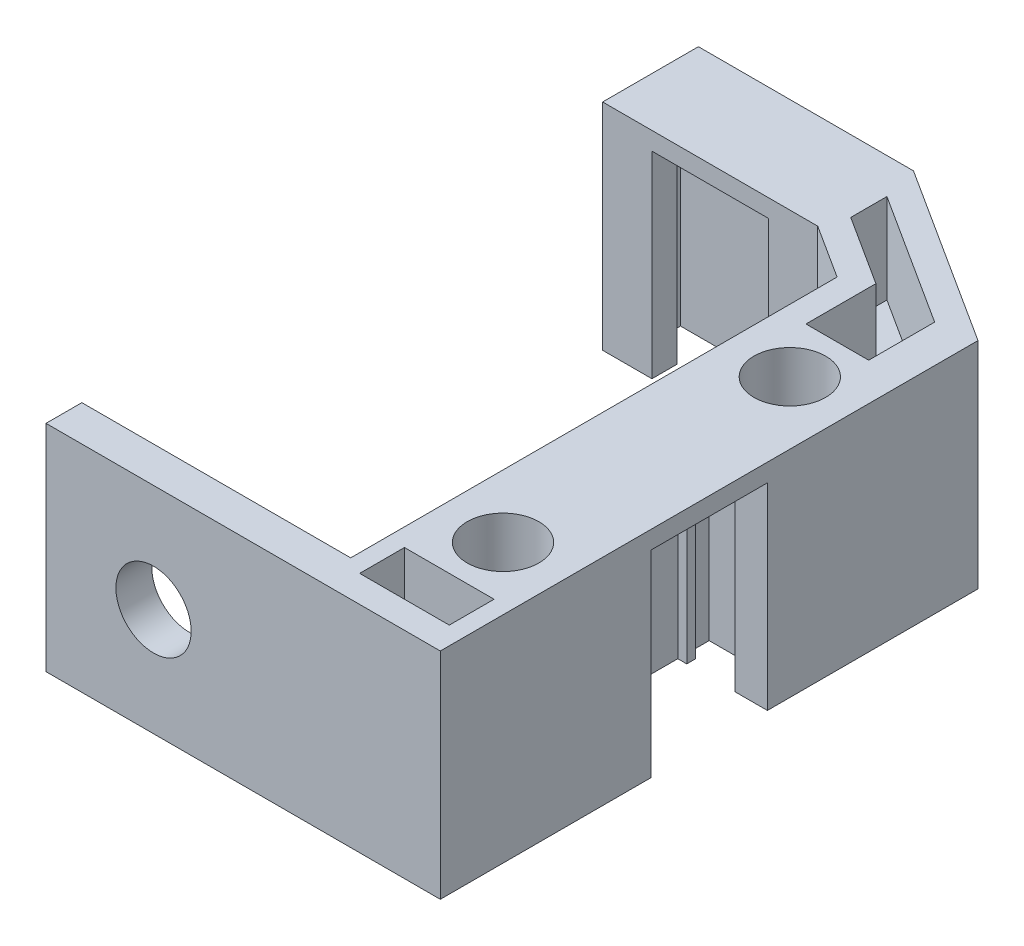
SolidWorks part; units mm, degrees
ref_plane "前视基准面" through (0, 0, 0) normal (0, 0, 1) x (1, 0, 0)
ref_plane "上视基准面" through (0, 0, 0) normal (0, 1, 0) x (1, 0, 0)
ref_plane "右视基准面" through (0, 0, 0) normal (1, 0, 0) x (0, 0, -1)
other "Configuration Table"
sketch "草图1" plane through (0, 0, 0) normal (0, 1, 0) x (1, 0, 0)
  line L0 (0, 0) -> (0, 2)
  line L1 (0, 36.4) -> (12, 36.4)
  line L2 (12, 36.4) -> (22, 30)
  line L3 (22, 30) -> (22, 0)
  line L4 (22, 0) -> (0, 0)
  line L5 (0, 31.0573) -> (12, 31.0573)
  line L6 (12, 31.0573) -> (15, 29.1373)
  line L7 (15, 29.1373) -> (15, 2)
  line L8 (15, 2) -> (0, 2)
  line L9 (0, 31.0573) -> (0, 36.4)
  point P11 (17, 33.2)
  dimension "D1" = 22
  dimension "D2" = 36.4
  dimension "D3" = 30
  dimension "D4" = 12
  dimension "D5" = 2
  dimension "D6" = 7
  dimension "D7" = 4.5
extrude "凸台-拉伸1" add sketch "草图1" along normal blind 12
sketch "草图2" plane through (0, 0, 0) normal (0, -1, 0) x (1, 0, 0)
  line L0 (12, -36.4) -> (0, -36.4) construction
  line L1 (1, -34.4) -> (11, -34.4)
  line L2 (1, -34.4) -> (1, -32.4573)
  line L3 (1, -32.4573) -> (2.75, -32.4573)
  line L4 (11, -34.4) -> (11, -32.4573)
  line L5 (1, -34.4) -> (11, -32.4573) construction
  line L6 (1, -32.4573) -> (11, -34.4) construction
  line L7 (0, -31.0573) -> (12, -31.0573) construction
  line L8 (0, -36.4) -> (0, -31.0573) construction
  line L9 (12.5, -32.3995) -> (12.5, -34.4178)
  line L10 (12.5, -34.4178) -> (19.9, -29.6818)
  line L11 (19.9, -29.6818) -> (19.9, -26)
  line L12 (19.9, -26) -> (16.4, -26)
  line L13 (16.4, -26) -> (16.4, -29.9035)
  line L14 (16.4, -29.9035) -> (12.5, -32.3995)
  line L15 (22, -30) -> (12, -36.4) construction
  line L16 (22, 0) -> (22, -30) construction
  line L17 (12, -31.0573) -> (15, -29.1373) construction
  line L18 (22, -30) -> (15, -30.369) construction
  line L19 (15, -29.1373) -> (15, -2) construction
  line L20 (17, -20) -> (17, -18.75)
  line L21 (17, -18.75) -> (17.5, -18.75)
  line L22 (17.5, -18.75) -> (17.5, -18.25)
  line L23 (17.5, -18.25) -> (17, -18.25)
  line L24 (17, -18.25) -> (17, -11.75)
  line L25 (17, -11.75) -> (17.5, -11.75)
  line L26 (17.5, -11.75) -> (17.5, -11.25)
  line L27 (17.5, -11.25) -> (17, -11.25)
  line L28 (17, -11.25) -> (17, -10)
  line L29 (17, -10) -> (20.2, -10)
  line L30 (20.2, -10) -> (20.2, -11.75)
  line L31 (20.2, -11.75) -> (22, -11.75)
  line L32 (22, -11.75) -> (22, -18.25)
  line L33 (22, -18.25) -> (20.2, -18.25)
  line L34 (20.2, -18.25) -> (20.2, -20)
  line L35 (20.2, -20) -> (17, -20)
  line L36 (22, 0) -> (22, -30) construction
  line L37 (22, -15) -> (15, -15) construction
  line L38 (0, 0) -> (22, 0) construction
  line L39 (16, -4) -> (21, -4)
  line L40 (16, -4) -> (16, -1.5)
  line L41 (16, -1.5) -> (21, -1.5)
  line L42 (21, -4) -> (21, -1.5)
  line L43 (16, -4) -> (21, -1.5) construction
  line L44 (16, -1.5) -> (21, -4) construction
  line L45 (2.75, -32.4573) -> (2.75, -31.0573)
  line L46 (2.75, -31.0573) -> (9.25, -31.0573)
  line L47 (9.25, -31.0573) -> (9.25, -32.4573)
  line L48 (9.25, -32.4573) -> (11, -32.4573)
  circle A0 centre (18.5, -23) radius 2
  circle A1 centre (18.5, -7) radius 2
  point P4 (6, -33.4287)
  point P44 (15, -15.5687)
  point P53 (18.5, -15)
  point P62 (18.5, -2.75)
  line M46 (22, -30) -> (22, 0)
  dimension "D17" = 4
  dimension "D1" = 10
  dimension "D2" = 2
  dimension "D3" = 1.4
  dimension "D4" = 1
  dimension "D5" = 3.5
  dimension "D6" = 1.4
  dimension "D7" = 1.4
  dimension "D8" = 1.5
  dimension "D9" = 1.4
  dimension "D10" = 2
  dimension "D11" = 1.8
  dimension "D12" = 6.5
  dimension "D13" = 10
  dimension "D14" = 0.5
  dimension "D15" = 0.5
  dimension "D16" = 0.5
  dimension "D19" = 16
  dimension "D18" = 3
  dimension "D20" = 3
  dimension "D21" = 1.5
  dimension "D22" = 2
  dimension "D23" = 1
  dimension "D24" = 3
  dimension "D25" = 6.5
  dimension "D26" = 1.75
extrude "切除-拉伸1" cut sketch "草图2" against normal blind 5 contours L13 L14 L9 L10 L11 L12 | L39 L42 L41 L40 region at (16.8771, 0, -29.6298) region at (18.5, 0, -2.75)
extrude "切除-拉伸3" cut sketch "草图2<3>" along normal blind 5 from surface contours L13 L14 L9 L10 L11 L12 | L39 L42 L41 L40 region at (16.8771, 0, -29.6298) region at (18.5, 0, -2.75) starting at face at (9.8, 12, -19.8052)
sketch "草图2<3>" plane through (0, 0, 0) normal (0, -1, 0) x (1, 0, 0) same geometry as "草图2"
extrude "切除-拉伸4" cut sketch "草图2<4>" against normal through all contours A0 | A1 region at (18.5, 0, -23) region at (18.5, 0, -7)
sketch "草图2<4>" plane through (0, 0, 0) normal (0, -1, 0) x (1, 0, 0) same geometry as "草图2"
extrude "切除-拉伸5" cut sketch "草图2<5>" against normal blind 11 contours L35 L34 L33 L31 L30 L29 L28 L27 L26 L25 L24 L23 L22 L21 L20 M46 | L1 L4 L3 L2 region at (6, 0, -32.8955) region at (19.2927, 0, -15)
sketch "草图2<5>" plane through (0, 0, 0) normal (0, -1, 0) x (1, 0, 0) same geometry as "草图2"
sketch "Sketch1" plane through (0, 0, -2) normal (0, 0, -1) x (-1, 0, 0)
  line L0 (0, 12) -> (0, 0) construction
  line L1 (-12, 12) -> (0, 12) construction
  circle A0 centre (-6, 6) radius 2.1
  point P4 (0, 6)
  point P7 (0, 0)
  point P8 (-6, 12)
  dimension "D1" = 4.2
extrude "Cut-Extrude1" cut sketch "Sketch1" against normal through all
equation "\"D20@草图2\"=\"D18@草图2\""
equation "\"D24@草图2\"=\"D18@草图2\""
equation "\"D26@草图2\"=(\"D1@草图2\"-\"D25@草图2\")/2"
